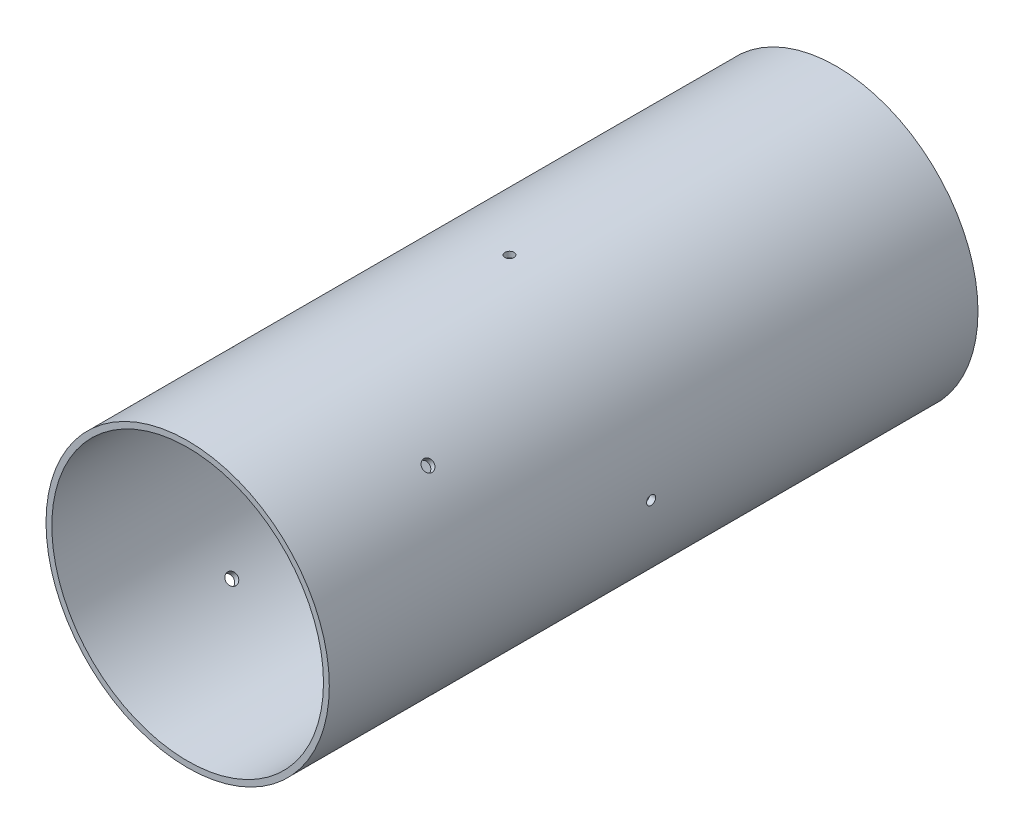
SolidWorks part; units mm, degrees
ref_plane "Front Plane" through (0, 0, 0) normal (0, 0, 1) x (1, 0, 0)
ref_plane "Top Plane" through (0, 0, 0) normal (0, 1, 0) x (1, 0, 0)
ref_plane "Right Plane" through (0, 0, 0) normal (1, 0, 0) x (0, 0, -1)
sketch "Sketch1" plane through (0, 0, 0) normal (0, 0, 1) x (1, 0, 0)
  circle A0 centre (0, 0) radius 49.53
  circle A1 centre (0, 0) radius 47.498
  dimension "D1" = 99.06
  dimension "D2" = 94.996
extrude "Boss-Extrude1" add sketch "Sketch1" along normal blind 226.822
extrude "Cut-Extrude1" cut sketch "Sketch2" against normal blind 12.7
sketch "Sketch2" plane through (-120.5803, -48.7382, -78.9954) normal (-0.7071, 0.7071, 0) x (0.7071, 0.7071, 0)
  circle A0 centre (119.7263, -256.7954) radius 1.9844
pattern_circular "CirPattern1" count 4 over 360 of "Cut-Extrude1"
extrude "Cut-Extrude2" cut sketch "Sketch3" against normal blind 25.4
sketch "Sketch3" plane through (-108.0218, -85.4992, -79.3332) normal (-0.866, 0.5, 0) x (0, 0, 1)
  circle A0 centre (196.8082, 128.0554) radius 2.3813
  circle A1 centre (190.4582, 128.0554) radius 2.3813
extrude "Cut-Extrude3" cut sketch "Sketch4" against normal blind 37.338
sketch "Sketch4" plane through (-33.6632, -130.5648, -80.7782) normal (1, 0, 0) x (0, 0, -1)
  circle A0 centre (-195.0782, 130.5648) radius 1.5875
  point P3 (-80.7782, 130.5648)
  point P4 (-195.0782, 181.3648)
pattern_circular "CirPattern2" count 4 over 360 about axis through (0, 0, 226.822) along (0, 0, -1) of "Cut-Extrude3" reverse direction yes
extrude "Cut-Extrude4" cut sketch "Sketch5" against normal blind 25.4
sketch "Sketch5" plane through (-120.5803, -48.7382, -78.9954) normal (-0.7071, 0.7071, 0) x (0.7071, 0.7071, 0)
  line L0 (68.6723, -129.7954) -> (170.7803, -129.7954) construction
  circle A0 centre (119.7263, -129.7954) radius 1.0922
pattern_circular "CirPattern3" count 2 over 360 of "Cut-Extrude4"
